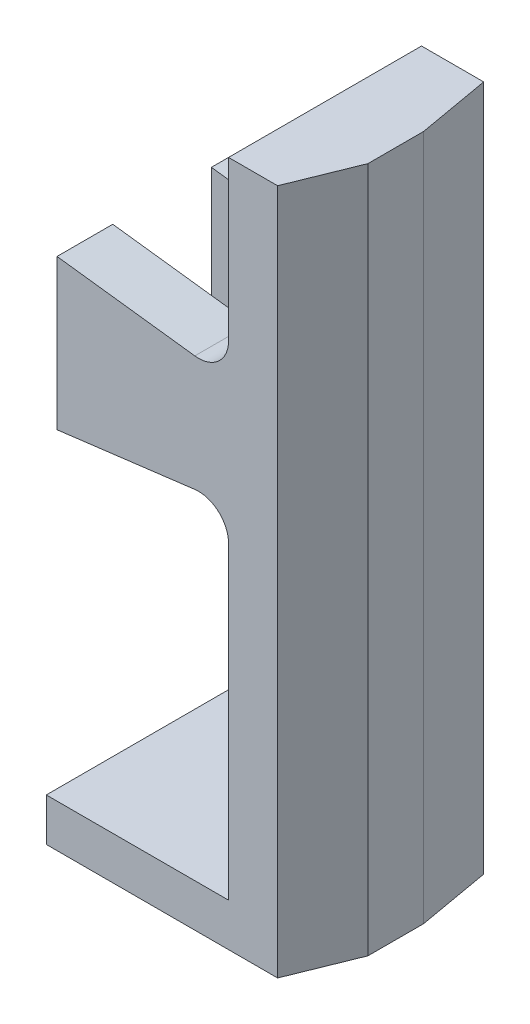
SolidWorks part; units mm, degrees
ref_plane "Front Plane" through (0, 0, 0) normal (1, 0, 0) x (0, 1, 0)
ref_plane "Top Plane" through (0, 0, 0) normal (0, 0, 1) x (0, 1, 0)
ref_plane "Right Plane" through (0, 0, 0) normal (0, 1, 0) x (-1, 0, 0)
sketch "Sketch1" plane through (0, 0, 0) normal (0, 0, 1) x (0, 1, 0)
  line L1 (-203.2, 76.2) -> (-190.5, 76.2)
  line L2 (-203.2, 76.2) -> (-203.2, 0)
  line L3 (-203.2, 0) -> (-190.5, 0)
  line L4 (-190.5, 76.2) -> (-190.5, 0)
  line L5 (-190.5, 0) -> (0, 0)
  line L6 (-190.5, 0) -> (-190.5, 22.225)
  line L7 (-190.5, 22.225) -> (0, 22.225)
  line L8 (0, 0) -> (0, 22.225)
  point P7 (0, 0)
  point P8 (0, 0)
  dimension "D1" = 12.7
  dimension "D2" = 22.225
  dimension "D3" = 203.2
  dimension "D4" = 76.2
extrude "Boss-Extrude1" add sketch "Sketch1" along normal mid plane 57.15 contours L4 L1 L2 L3 | L5 L8 L7 L4 region at (-38.1, -196.85, 0) region at (-11.1125, -95.25, 0)
chamfer "Chamfer1" distance 19.05 angle 22 1 edges at (0, -101.6, 28.575) first distance on face at (0, -101.6, 0)
chamfer "Chamfer2" distance 3.81 angle 80 1 edges at (0, -101.6, -28.575) first distance on face at (-32.8083, -131.2333, -28.575)
sketch "Sketch3" plane through (0, 0, -28.575) normal (0, 0, -1) x (1, 0, 0)
  line L0 (-22.225, 88.9) -> (-73.025, 95.25)
  line L1 (-22.225, 190.5) -> (-22.225, 0) construction
  line L2 (-73.025, 95.25) -> (-73.025, 50.8)
  line L3 (-73.025, 50.8) -> (-22.225, 57.15)
  line L4 (-22.225, 57.15) -> (-22.225, 88.9)
  line L7 (-3.81, 0) -> (-22.225, 0) construction
  point P8 (-12.7, 130.553)
  dimension "D1" = 44.45
  dimension "D2" = 31.75
  dimension "D3" = 6.35
  dimension "D4" = 57.15
  dimension "D5" = 50.8
extrude "Boss-Extrude2" add sketch "Sketch3" against normal blind 11.43
sketch "Sketch4" plane through (0, 0, 28.575) normal (0, 0, 1) x (1, 0, 0)
  line L0 (-22.225, -57.15) -> (-73.025, -50.8)
  line L1 (-73.025, -50.8) -> (-73.025, -95.25)
  line L2 (-73.025, -95.25) -> (-22.225, -88.9)
  line L3 (-22.225, -88.9) -> (-22.225, -57.15)
  line L4 (-22.225, -190.5) -> (-22.225, 0) construction
  line L5 (-7.6967, 0) -> (-22.225, 0) construction
  line L6 (-73.025, -95.25) -> (-73.025, -50.8) construction
  point P6 (-67.3636, -44.038)
  dimension "D1" = 44.45
  dimension "D2" = 31.75
  dimension "D3" = 6.35
  dimension "D4" = 57.15
extrude "Boss-Extrude3" add sketch "Sketch4" against normal blind 16.51
fillet "Fillet1" radius 8.89 4 edges at (-22.225, -88.9, -22.86) (-22.225, -57.15, -22.86) (-22.225, -88.9, 20.32) (-22.225, -57.15, 20.32)
chamfer "Chamfer3" distance 2.54 angle 45 2 edges
